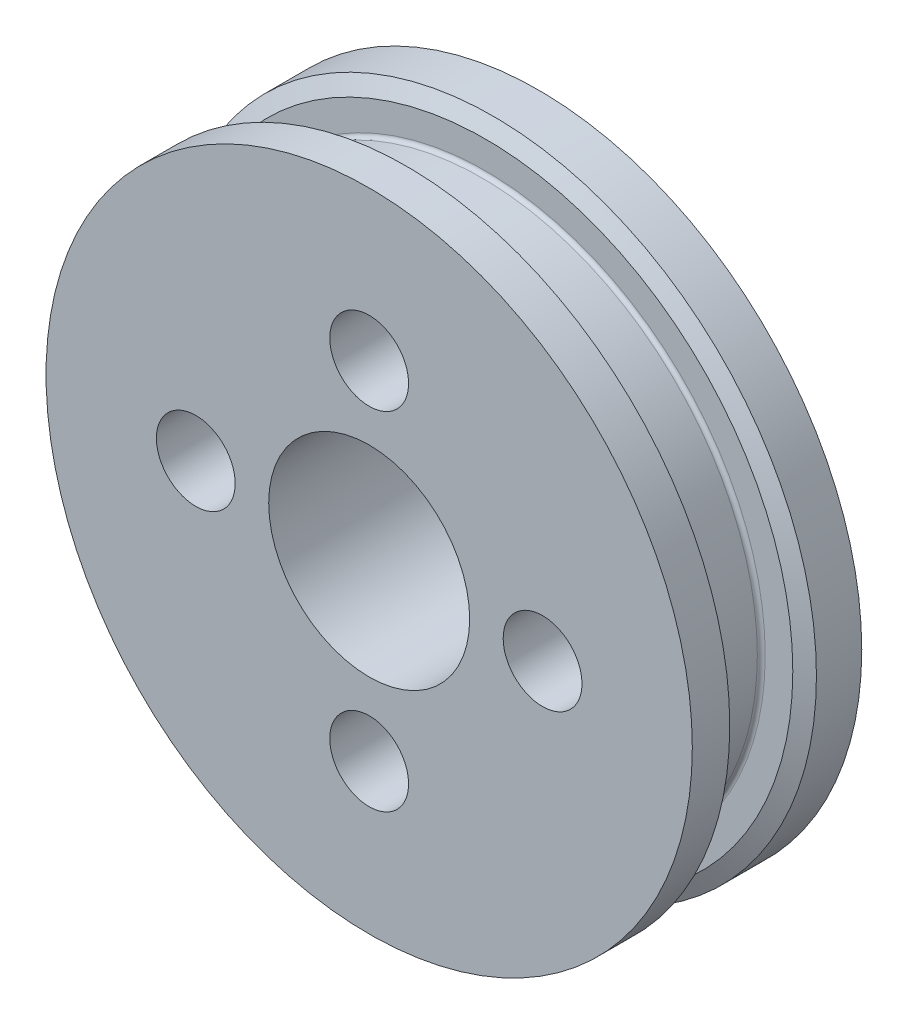
SolidWorks part; units mm, degrees
ref_plane "Front Plane" through (0, 0, 0) normal (0, 0, 1) x (1, 0, 0)
ref_plane "Top Plane" through (0, 0, 0) normal (0, 1, 0) x (1, 0, 0)
ref_plane "Right Plane" through (0, 0, 0) normal (1, 0, 0) x (0, 0, -1)
sketch "Sketch2" plane through (0, 0, 0) normal (1, 0, 0) x (0, 0, -1)
  line L0 (0, 6.477) -> (0, 20.828)
  line L1 (0, 20.828) -> (2.413, 20.828)
  line L2 (2.921, 19.812) -> (2.921, 17.78)
  line L3 (2.921, 17.78) -> (7.493, 17.78)
  line L4 (7.493, 17.78) -> (7.493, 19.812)
  line L5 (8.001, 20.828) -> (10.922, 20.828)
  line L6 (10.922, 20.828) -> (10.922, 6.477)
  line L8 (0, 6.477) -> (10.922, 6.477)
  line L9 (0, 6.477) -> (0, 0) construction
  line L10 (0, 0) -> (10.7816, 0) construction
  line L11 (7.493, 19.812) -> (8.001, 20.828)
  line L12 (2.413, 20.828) -> (2.921, 19.812)
  point P4 (2.921, 20.828)
  point P7 (7.493, 20.828)
  dimension "D1" = 17.78
  dimension "D2" = 10.922
  dimension "D3" = 3.048
  dimension "D4" = 6.477
  dimension "D5" = 4.572
  dimension "D6" = 1.016
  dimension "D7" = 0.508
  dimension "D8" = 0.508
  dimension "D9" = 1.016
  dimension "D10" = 2.921
revolve "Revolve1" add sketch "Sketch2" angle 360 about L10
sketch "Sketch3" plane through (0, 0, -10.922) normal (0, 0, -1) x (-1, 0, 0)
  line L1 (-8.255, -8.255) -> (8.255, -8.255)
  line L2 (-8.255, -8.255) -> (-8.255, 8.255)
  line L3 (-8.255, 8.255) -> (8.255, 8.255)
  line L4 (8.255, -8.255) -> (8.255, 8.255)
  circle A0 centre (0, 0) radius 6.477 construction
  circle A1 centre (0, 0) radius 6.477
  point P4 (8.255, 0)
  point P6 (0, 8.255)
  dimension "D1" = 16.51
extrude "Boss-Extrude1" add sketch "Sketch3" along normal blind 3.175
ref_plane "Plane1" through (0, 0, -5.461) normal (0, 0, -1) x (-1, 0, 0)
sketch "Sketch4" plane through (0, 0, -10.922) normal (0, 0, -1) x (-1, 0, 0)
  line L0 (0, 11.176) -> (0, 0) construction
  line L1 (0, 0) -> (0, -11.176) construction
  line L2 (-11.176, 0) -> (0, 0) construction
  line L3 (0, 0) -> (11.176, 0) construction
  circle A0 centre (0, 11.176) radius 2.54
  circle A1 centre (11.176, 0) radius 2.54
  circle A2 centre (0, -11.176) radius 2.54
  circle A3 centre (-11.176, 0) radius 2.54
  dimension "D1" = 5.08
  dimension "D2" = 11.176
extrude "Cut-Extrude1" cut sketch "Sketch4" against normal through all both and the other way through all
fillet "Fillet1" radius 0.254 2 edges at (17.78, 0, -7.493) (17.78, 0, -2.921)
